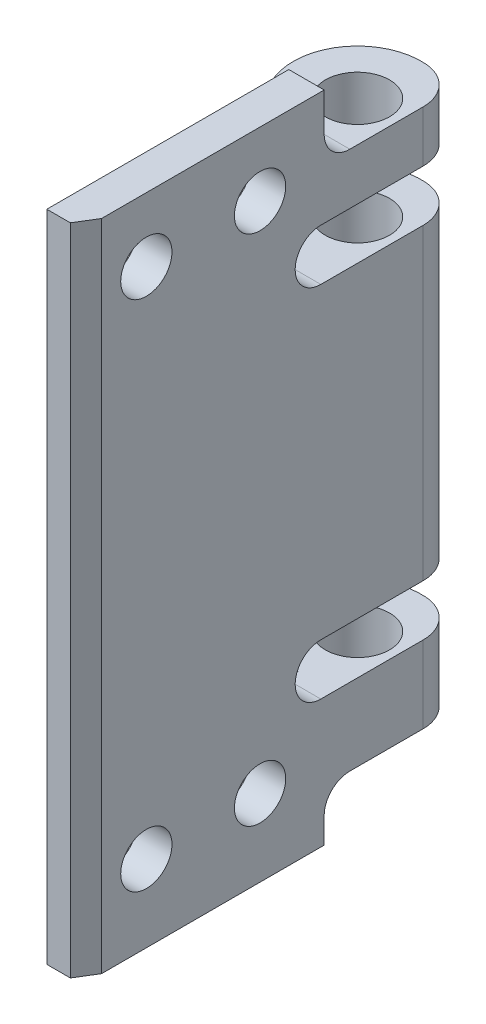
SolidWorks part; units mm, degrees
ref_plane "Front Plane" through (0, 0, 0) normal (0, 0, 1) x (1, 0, 0)
ref_plane "Top Plane" through (0, 0, 0) normal (0, 1, 0) x (1, 0, 0)
ref_plane "Right Plane" through (0, 0, 0) normal (1, 0, 0) x (0, 0, -1)
sketch "Sketch1" plane through (0, 0, 0) normal (0, 1, 0) x (1, 0, 0)
  line L0 (143.3333, 493) -> (716.6667, 493) construction
  line L1 (57.1966, 9.0284) -> (57.1966, 28.64)
  line L4 (59.9567, 29.7327) -> (59.9567, 10.5387)
  line L5 (59.9567, 10.5387) -> (59.0306, 9.0284)
  line L6 (59.0306, 9.0284) -> (57.1966, 9.0284)
  line L7 (59.9567, 29.7327) -> (59.9567, 37.5187)
  line L8 (64.209, 27.9079) -> (65.0991, 27.0179)
  line L13 (64.654, 7.1943) -> (64.654, 5.5805)
  line L16 (63.4817, 13.8234) -> (63.1068, 13.4485)
  arc A1 (59.9567, 37.5187) -> (57.1966, 28.64) centre (56.819, 33.6257) ccw
  circle A4 centre (56.819, 33.6257) radius 2.5
extrude "Boss-Extrude1" add sketch "Sketch1" along normal blind 51 contours L13 L8 L4 L16 | L1 L6 L5 L4 A4 region at (57.3647, 0, -25.9901)
sketch "Sketch2" plane through (59.9567, 0, 0) normal (1, 0, 0) x (0, 0, -1)
  line L0 (0, 0) -> (0, 10) construction
  line L2 (39.1338, 10) -> (25.6338, 10)
  line L11 (39.1338, 14) -> (39.1338, 10)
  line L14 (39.1338, 14) -> (27.8951, 14)
  line L15 (25.6338, 10) -> (25.6338, 14)
  line L18 (25.6338, 14) -> (27.8951, 14)
extrude "Cut-Extrude1" cut sketch "Sketch2" against normal mid plane 30
sketch "Sketch3" plane through (59.9567, 0, 0) normal (1, 0, 0) x (0, 0, -1)
  line L0 (9.0284, 51) -> (9.0284, 40) construction
  line L1 (9.0284, 51) -> (9.0284, 0) construction
  line L3 (25.6338, 14) -> (25.6338, 47.1784) construction
  line L12 (41.7113, 42) -> (27.8951, 42)
  line L14 (41.7113, 42) -> (41.7113, 38)
  line L18 (41.7113, 38) -> (25.6338, 38)
  line L20 (25.6338, 38) -> (25.6338, 42)
  line L21 (25.6338, 42) -> (27.8951, 42)
extrude "Cut-Extrude2" cut sketch "Sketch3" against normal mid plane 25
sketch "Sketch4" plane through (59.9567, 0, 0) normal (1, 0, 0) x (0, 0, -1)
  line L1 (38.8451, 0) -> (38.8451, 4)
  line L4 (38.8451, 51) -> (30.0565, 51)
  line L6 (38.8451, 4) -> (27.8951, 4)
  line L13 (27.8951, 4) -> (27.8951, 0)
  line L17 (38.8451, 0) -> (27.8951, 0)
  line L20 (27.8951, 47) -> (27.8951, 51)
  line L21 (27.8951, 51) -> (30.0565, 51)
  line L23 (38.8451, 51) -> (38.8451, 46)
  line L24 (38.8451, 46) -> (27.8951, 46)
  line L25 (27.8951, 46) -> (27.8951, 47)
extrude "Cut-Extrude3" cut sketch "Sketch4" against normal mid plane 50
sketch "Sketch5" plane through (57.1966, 0, 0) normal (-1, 0, 0) x (0, 0, 1)
  line L0 (-27.8951, 51) -> (-22.8951, 51) construction
  line L1 (-9.0284, 51) -> (-27.8951, 51) construction
  line L2 (-22.8951, 51) -> (-22.8951, 46) construction
  line L3 (-18.4617, 51) -> (-18.4617, 40.0063) construction
  line L4 (-27.8951, 26) -> (-14.7419, 26) construction
  circle A0 centre (-22.8951, 46) radius 2
  circle A1 centre (-14.0284, 46) radius 2
  circle A2 centre (-14.0284, 6) radius 2
  circle A3 centre (-22.8951, 6) radius 2
extrude "Cut-Extrude4" cut sketch "Sketch5" against normal blind 10
fillet "Fillet4" radius 2 1 edges at (57.1966, 26, -28.64)
fillet "Fillet5" radius 3 3 edges at (59.9567, 7, -37.5187) (59.9567, 26, -37.5187) (59.9567, 44, -37.5187)
fillet "Fillet6" radius 2 6 edges at (58.5767, 4, -27.8951) (58.5767, 46, -27.8951) (58.5767, 10, -25.6338) (58.5767, 14, -25.6338) (58.5767, 42, -25.6338) (58.5767, 38, -25.6338)
